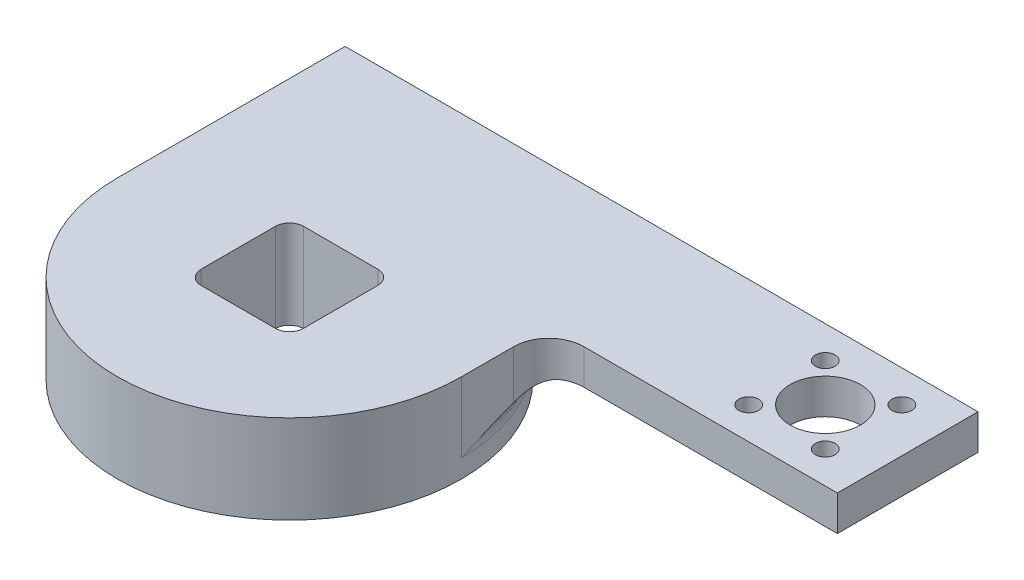
SolidWorks part; units mm, degrees
material "6061-T6 (SS)"
ref_plane "Front Plane" through (0, 0, 0) normal (0, 0, 1) x (1, 0, 0)
ref_plane "Top Plane" through (0, 0, 0) normal (0, 1, 0) x (1, 0, 0)
ref_plane "Right Plane" through (0, 0, 0) normal (1, 0, 0) x (0, 0, -1)
sketch "Sketch1" plane through (0, 0, 0) normal (0, 1, 0) x (1, 0, 0)
  line L0 (-1.1049, 0) -> (-31.0896, 0) construction
  line L1 (-1.1049, 0) -> (31.0896, 0) construction
  circle A0 centre (0, 0) radius 31.0896
  dimension "D1" = 62.1792
extrude "Boss-Extrude1" add sketch "Sketch1" along normal blind 16.002
sketch "Sketch2" plane through (0, 16.002, 0) normal (0, 1, 0) x (1, 0, 0)
  line L0 (0, 0) -> (-31.0896, 0) construction
  line L1 (0, 0) -> (31.0896, 0) construction
  line L2 (-31.0896, 0) -> (-31.0896, 41.148)
  line L3 (-31.0896, 41.148) -> (83.2104, 41.148)
  line L4 (83.2104, 41.148) -> (83.2104, 15.748)
  line L5 (31.0896, 0) -> (31.0896, 15.748)
  line L6 (31.0896, 15.748) -> (83.2104, 15.748)
  circle A0 centre (0, 0) radius 31.0896 construction
  circle A2 centre (0, 0) radius 31.0896
  arc A3 (-31.0896, 0) -> (31.0896, 0) centre (0, 0) ccw
  dimension "D1" = 0
  dimension "D2" = 114.3
  dimension "D3" = 25.4
  dimension "D4" = 15.748
extrude "Boss-Extrude2" add sketch "Sketch2" against normal blind 6.35
fillet "Fillet1" radius 6.35 1 edges at (0, 9.652, -31.0896)
fillet "Fillet2" radius 6.35 1 edges at (31.0896, 12.5511, -15.748)
sketch "Sketch4" plane through (0, 16.002, 0) normal (0, 1, 0) x (1, 0, 0)
  line L0 (83.2104, 41.148) -> (58.166, 41.148) construction
  line L1 (83.2104, 41.148) -> (-31.0896, 41.148) construction
  line L2 (58.166, 41.148) -> (58.166, 28.448) construction
  line L3 (58.166, 28.448) -> (78.486, 28.448) construction
  line L4 (68.326, 28.448) -> (75.2408, 35.3628) construction
  line L5 (68.326, 28.448) -> (75.2408, 21.5332) construction
  line L6 (68.326, 28.448) -> (61.4112, 21.5332) construction
  line L7 (68.326, 28.448) -> (61.4112, 35.3628) construction
  circle A0 centre (61.4112, 35.3628) radius 1.778
  circle A1 centre (75.2408, 35.3628) radius 1.778
  circle A2 centre (75.2408, 21.5332) radius 1.778
  circle A3 centre (68.326, 28.448) radius 6.35
  circle A4 centre (61.4112, 21.5332) radius 1.778
extrude "Cut-Extrude2" cut sketch "Sketch4" against normal up to next
sketch "Sketch5" plane through (0, 16.002, 0) normal (0, 1, 0) x (1, 0, 0)
  line L1 (9.2497, 9.2497) -> (-9.2497, 9.2497)
  line L2 (9.2497, 9.2497) -> (9.2497, -9.2497)
  line L3 (9.2497, -9.2497) -> (-9.2497, -9.2497)
  line L4 (-9.2497, 9.2497) -> (-9.2497, -9.2497)
  line L5 (9.2497, 9.2497) -> (-9.2497, -9.2497) construction
  line L6 (9.2497, -9.2497) -> (-9.2497, 9.2497) construction
  point P0 (0, 0)
  dimension "D1" = 26.162
extrude "Cut-Extrude3" cut sketch "Sketch5" against normal up to next
fillet "Fillet3" radius 2.54 1 edges at (-9.2497, 8.001, -9.2497)
fillet "Fillet4" radius 2.54 1 edges at (9.2497, 8.001, -9.2497)
fillet "Fillet5" radius 2.54 1 edges at (9.2497, 8.001, 9.2497)
fillet "Fillet6" radius 2.54 1 edges at (-9.2497, 8.001, 9.2497)
